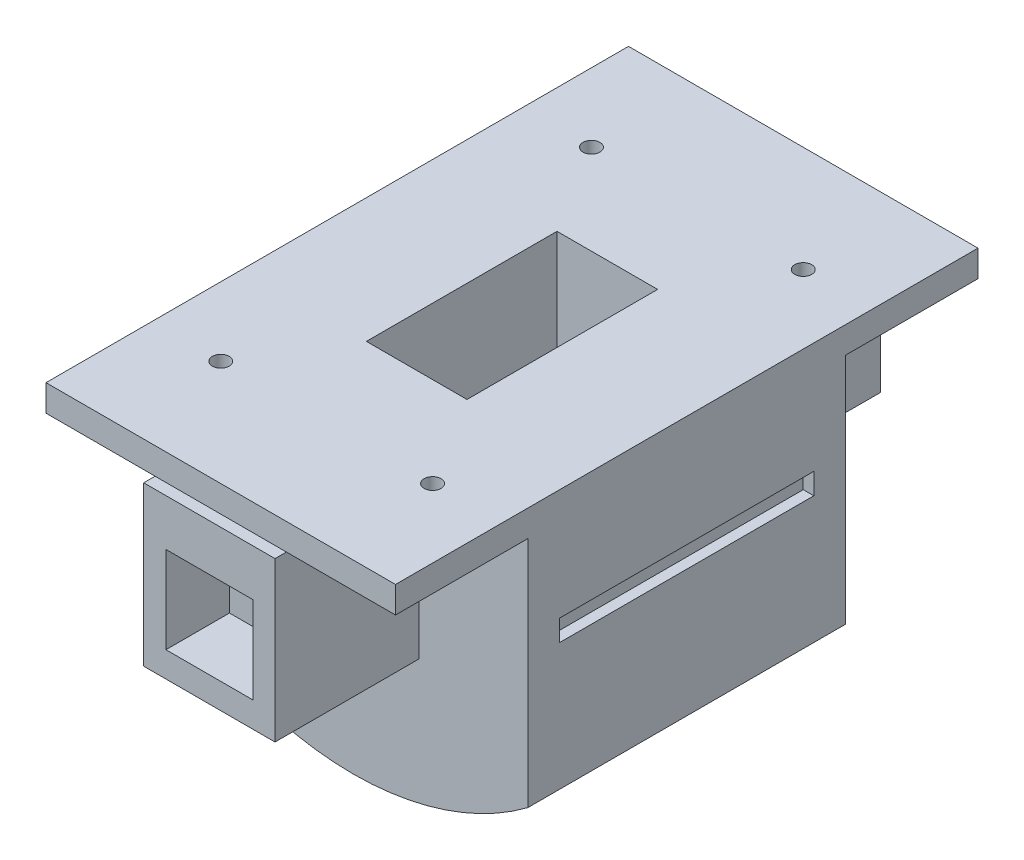
SolidWorks part; units mm, degrees
ref_plane "Front Plane" through (0, 0, 0) normal (0, 0, 1) x (1, 0, 0)
ref_plane "Top Plane" through (0, 0, 0) normal (0, 1, 0) x (1, 0, 0)
ref_plane "Right Plane" through (0, 0, 0) normal (1, 0, 0) x (0, 0, -1)
sketch "Sketch1" plane through (0, 0, 0) normal (0, 0, 1) x (1, 0, 0)
  line L0 (0, 0) -> (0, -42) construction
  line L1 (0, 0) -> (55, 0)
  line L2 (55, 0) -> (-55, 0)
  arc A0 (-55, 0) -> (55, 0) centre (0, 0) ccw
  dimension "D2" = 55
  dimension "D1" = 42
extrude "Boss-Extrude1" add sketch "Sketch1" along normal blind 30 and the other way blind 30 contours L2 A0 L1 region at (0, -23.3427, 0)
sketch "Sketch2" plane through (0, 0, 0) normal (0, 0, 1) x (1, 0, 0)
  line L1 (0, 0) -> (-9.5, 0)
  line L3 (2.8861, -42) -> (-9.5, -42)
  line L4 (-9.5, 0) -> (-9.5, -42)
  line L5 (0, 0) -> (9.5, 0)
  line L7 (2.8861, -42) -> (9.5, -42)
  line L8 (9.5, 0) -> (9.5, -42)
  circle A0 centre (0, 0) radius 42
  dimension "D1" = 84
  dimension "D2" = 9.5
  dimension "D3" = 9.5
  dimension "D4" = 42
extrude "Cut-Extrude1" cut sketch "Sketch2" against normal blind 18 and the other way blind 18 contours L4 A0 L8 L5 L1 | A0 L4 L3 | A0 L3 L7 L8 region at (0, -20.8208, 0) region at (-7.1312, -41.6742, 0) region at (7.1312, -41.6742, 0)
sketch "Sketch3" plane through (0, 0, 30) normal (0, 0, 1) x (1, 0, 0)
  line L0 (0, 0) -> (0, -28.5435) construction
  line L1 (-54.8544, -4) -> (-33, -4)
  line L2 (-54.8544, -4) -> (-54.8544, -49)
  line L3 (-54.8544, -49) -> (-33, -49)
  line L4 (-33, -4) -> (-33, -49)
  line L5 (55, 0) -> (-55, 0) construction
  line L6 (33, -4) -> (33, -49)
  line L7 (54.8544, -49) -> (33, -49)
  line L8 (54.8544, -4) -> (54.8544, -49)
  line L9 (54.8544, -4) -> (33, -4)
  arc A0 (-55, 0) -> (55, 0) centre (0, 0) ccw construction
  dimension "D1" = 4
  dimension "D2" = 33
  dimension "D3" = 45
extrude "Cut-Extrude2" cut sketch "Sketch3" against normal through all
sketch "Sketch4" plane through (0, 0, 0) normal (0, 1, 0) x (1, 0, 0)
  line L0 (55, 30) -> (-55, 30) construction
  line L1 (55, 30) -> (55, -30) construction
  line L2 (0, 0) -> (0, 55.9923) construction
  line L3 (0, 0) -> (36.0907, 0) construction
  circle A0 centre (45, 20) radius 1.6
  circle A1 centre (45, -20) radius 1.6
  circle A2 centre (-45, -20) radius 1.6
  circle A3 centre (-45, 20) radius 1.6
  dimension "D1" = 3.2
  dimension "D2" = 10
  dimension "D3" = 10
extrude "Cut-Extrude3" cut sketch "Sketch4" against normal through all
sketch "Sketch6" plane through (33, 0, 0) normal (1, 0, 0) x (0, 0, -1)
  line L0 (-30, -4) -> (-30, -44) construction
  line L1 (-24, -16) -> (24, -16)
  line L2 (-24, -16) -> (-24, -20)
  line L3 (-24, -20) -> (24, -20)
  line L4 (24, -16) -> (24, -20)
  line L5 (30, -4) -> (30, -44) construction
  line L6 (30, -4) -> (-30, -4) construction
  dimension "D1" = 6
  dimension "D2" = 6
  dimension "D3" = 12
  dimension "D4" = 4
extrude "Cut-Extrude5" cut sketch "Sketch6" against normal blind 2
sketch "Sketch9" plane through (0, 0, 0) normal (0, 1, 0) x (1, 0, 0)
  line L5 (-55, 30) -> (-33, 30)
  line L6 (-55, 30) -> (-55, -30)
  line L7 (-55, -30) -> (-33, -30)
  line L8 (-33, 30) -> (-33, -30)
  line L9 (55, 30) -> (33, 30)
  line L10 (55, 30) -> (55, -30)
  line L11 (55, -30) -> (33, -30)
  line L12 (33, 30) -> (33, -30)
extrude "Cut-Extrude7" cut sketch "Sketch9" against normal through all
sketch "Sketch10" plane through (0, 0, 0) normal (0, 1, 0) x (1, 0, 0)
  line L1 (-33, 30) -> (33, 30)
  line L2 (-33, 30) -> (-33, -30)
  line L3 (-33, -30) -> (33, -30)
  line L4 (33, 30) -> (33, -30)
  line L5 (33, -30) -> (-33, -30)
  line L6 (33, -30) -> (33, -55)
  line L7 (33, -55) -> (-33, -55)
  line L8 (-33, -30) -> (-33, -55)
  line L9 (-33, 30) -> (33, 30)
  line L10 (-33, 30) -> (-33, 55)
  line L11 (-33, 55) -> (33, 55)
  line L12 (33, 30) -> (33, 55)
  line L13 (-9.5, 18) -> (9.5, 18)
  line L14 (-9.5, 18) -> (-9.5, -18)
  line L15 (-9.5, -18) -> (9.5, -18)
  line L16 (9.5, 18) -> (9.5, -18)
  line M3 (-33, 30) -> (-33, -30)
  line M4 (-33, -30) -> (33, -30)
  line M5 (33, -30) -> (33, 30)
  line M6 (33, 30) -> (-33, 30)
  line M7 (9.5, -18) -> (-9.5, -18)
  line M8 (-9.5, -18) -> (-9.5, 18)
  line M9 (-9.5, 18) -> (9.5, 18)
  line M10 (9.5, 18) -> (9.5, -18)
  dimension "D1" = 25
  dimension "D2" = 25
extrude "Boss-Extrude2" add sketch "Sketch10" along normal blind 5 contours L12 L11 L10 M6 | M6 M3 M4 M5 M10 M7 M8 M9 | L8 L7 L6 M4 region at (0, 0, -42.5) region at (0, 0, -29.108) region at (0, 0, 42.5)
sketch "Sketch11" plane through (0, 5, 0) normal (0, 1, 0) x (1, 0, 0)
  line L0 (0, 0) -> (-22.9202, 0) construction
  line L1 (-22.9202, 0) -> (0, 0) construction
  circle A0 centre (-20, 35) radius 1.6
  circle A1 centre (20, 35) radius 1.6
  circle A2 centre (-20, -35) radius 1.6
  circle A3 centre (20, -35) radius 1.6
  dimension "D1" = 3.2
  dimension "D2" = 35
  dimension "D3" = 20
  dimension "D5" = 40
  dimension "D4" = 2
extrude "Cut-Extrude8" cut sketch "Sketch11" against normal through all
sketch "Sketch13" plane through (0, 0, -30) normal (0, 0, -1) x (-1, 0, 0)
  line L0 (33, 0) -> (-33, 0) construction
  line L11 (-18.4, 0) -> (-18.4, 5) construction
  line L12 (-12.4, 0) -> (12.4, 0)
  line L13 (-12.4, 0) -> (-12.4, -30)
  line L14 (-12.4, -30) -> (12.4, -30)
  line L15 (12.4, 0) -> (12.4, -30)
  line L16 (18.4, 5) -> (18.4, 0) construction
  point P0 (0, -17)
  dimension "D5" = 6
  dimension "D6" = 30
  dimension "D7" = 6
extrude "Boss-Extrude3" add sketch "Sketch13" along normal blind 27.15
sketch "Sketch14" plane through (0, 0, -57.15) normal (0, 0, -1) x (-1, 0, 0)
  line L0 (33, -44) -> (33, 0) construction
  line L5 (33, 0) -> (12.4, 0) construction
  line L6 (0, -17) -> (0, 0) construction
  line L7 (-8, -9) -> (8, -9)
  line L8 (-8, -9) -> (-8, -25)
  line L9 (-8, -25) -> (8, -25)
  line L10 (8, -9) -> (8, -25)
  line L11 (-8, -9) -> (8, -25) construction
  line L12 (-8, -25) -> (8, -9) construction
  line L14 (-8.2, -8.8) -> (8.2, -8.8)
  line L15 (-8.2, -8.8) -> (-8.2, -25.2)
  line L16 (-8.2, -25.2) -> (8.2, -25.2)
  line L17 (8.2, -8.8) -> (8.2, -25.2)
  line L18 (-8.2, -8.8) -> (8.2, -25.2) construction
  line L19 (-8.2, -25.2) -> (8.2, -8.8) construction
  point P4 (0, -17)
  dimension "D1" = 16
  dimension "D2" = 9
  dimension "D3" = 16
  dimension "D4" = 25
  dimension "D5" = 17
  dimension "D6" = 0.2
  dimension "D7" = 0.2
extrude "Cut-Extrude9" cut sketch "Sketch14" against normal blind 12 contours L10 L7 L8 L9 | L17 L14 L15 L16 L7 L10 L9 L8 region at (0, -17, -57.15) region at (0, -8.8232, -57.15)
ref_plane "Plane1" through (0, 0, 0) normal (0, 0, -1) x (-1, 0, 0)
mirror "Mirror2" about plane through (0, 0, 0) normal (0, 0, -1) of "Boss-Extrude3"
mirror "Mirror3" about plane through (0, 0, 0) normal (0, 0, -1) of "Cut-Extrude9"
